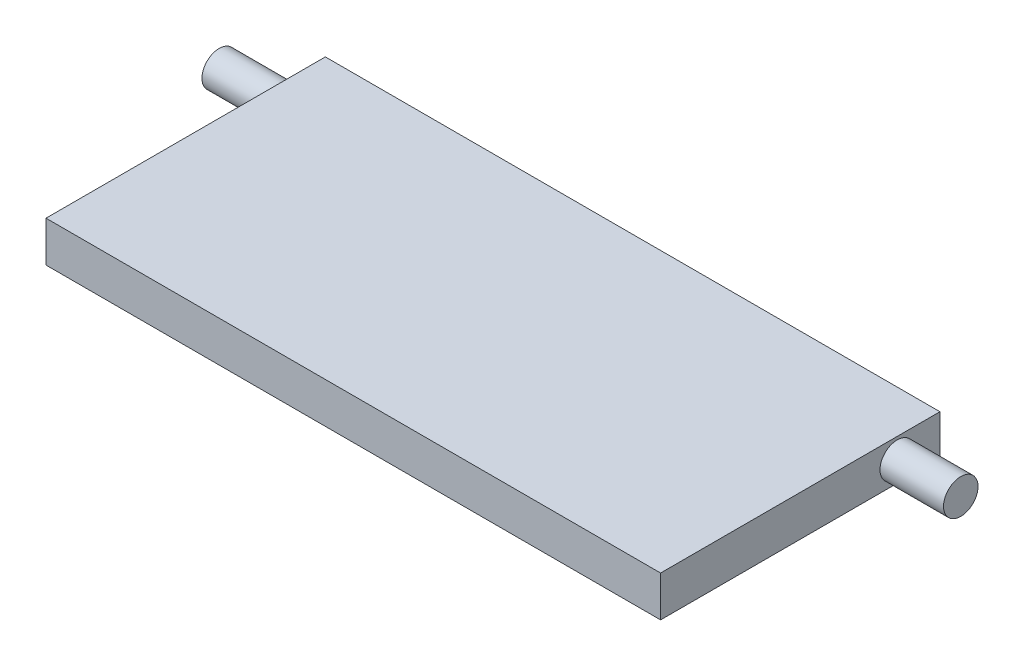
SolidWorks part; units mm, degrees
ref_plane "Front Plane" through (0, 0, 0) normal (0, 0, 1) x (1, 0, 0)
ref_plane "Top Plane" through (0, 0, 0) normal (0, 1, 0) x (1, 0, 0)
ref_plane "Right Plane" through (0, 0, 0) normal (1, 0, 0) x (0, 0, -1)
sketch "Sketch1" plane through (0, 0, 0) normal (0, 1, 0) x (1, 0, 0)
  line L0 (-60.5, 22.5) -> (-73, 22.5)
  line L1 (-60.5, 27.5) -> (60.5, 27.5)
  line L2 (-60.5, 27.5) -> (-60.5, -27.5)
  line L3 (-60.5, -27.5) -> (60.5, -27.5)
  line L4 (60.5, 27.5) -> (60.5, -27.5)
  line L5 (-60.5, 27.5) -> (60.5, -27.5) construction
  line L6 (-60.5, -27.5) -> (60.5, 27.5) construction
  line L7 (-73, 22.5) -> (-73, 15.7)
  line L8 (-73, 15.7) -> (-60.5, 15.7)
  line L9 (0, -27.5) -> (0, 27.5) construction
  line L10 (-73, 19.1) -> (-60.5, 19.1)
  point P0 (0, 0)
  dimension "D1" = 121
  dimension "D2" = 55
  dimension "D3" = 6.8
  dimension "D4" = 5
  dimension "D5" = 12.5
extrude "Boss-Extrude1" add sketch "Sketch1" along normal mid plane 8 contours L4 L1 L2 L3 region at (0, 0, 0)
revolve "Revolve1" add sketch "Sketch1<3>" angle 360 about L10 region at (-66.75, 0, -20.8)
sketch "Sketch1<3>" plane through (0, 0, 0) normal (0, 1, 0) x (1, 0, 0) same geometry as "Sketch1"
mirror "Mirror1" about plane through (0, 0, 0) normal (1, 0, 0) of "Revolve1"
